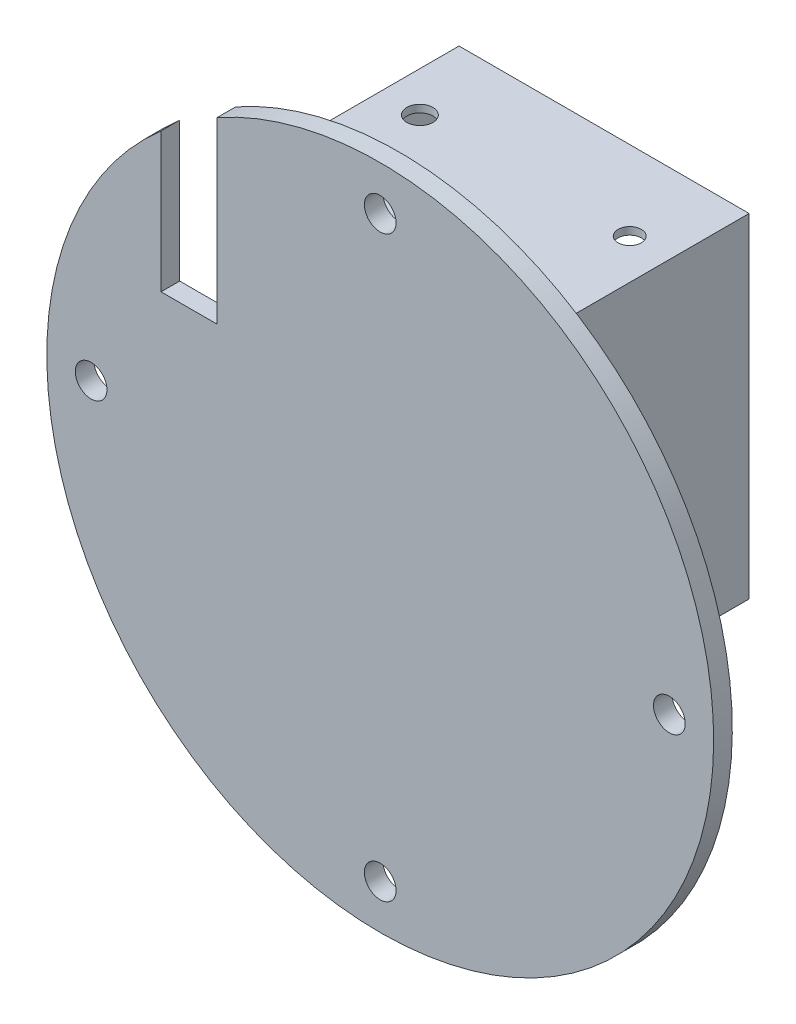
SolidWorks part; units mm, degrees
ref_plane "Front Plane" through (0, 0, 0) normal (0, 0, 1) x (1, 0, 0)
ref_plane "Top Plane" through (0, 0, 0) normal (0, 1, 0) x (1, 0, 0)
ref_plane "Right Plane" through (0, 0, 0) normal (1, 0, 0) x (0, 0, -1)
sketch "Sketch1" plane through (0, 0, 0) normal (0, 0, 1) x (1, 0, 0)
  circle A0 centre (0, 0) radius 35.75
  dimension "D1" = 71.5
extrude "Boss-Extrude1" add sketch "Sketch1" along normal blind 2 contours A0
sketch "Sketch2" plane through (0, 0, 0) normal (0, 0, -1) x (-1, 0, 0)
  line L52 (14.75, 26) -> (-14.75, 26)
  line L59 (15.55, -9) -> (15.55, 26.8)
  line L60 (15.55, 26.8) -> (-15.55, 26.8)
  line L61 (-15.55, 26.8) -> (-15.55, -9)
  line L68 (-14.75, 26) -> (-14.75, -9)
  line L70 (14.75, 26) -> (14.75, -9)
  line L71 (14.75, -9) -> (15.55, -9)
  line L72 (-14.75, -9) -> (-15.55, -9)
  dimension "D1" = 35
  dimension "D2" = 29.5
  dimension "D3" = 0.8
  dimension "D4" = 0.8
  dimension "D5" = 35
  dimension "D6" = 0.8
  dimension "D7" = 26
  dimension "D8" = 14.75
extrude "Boss-Extrude2" add sketch "Sketch2" along normal blind 22
sketch "Sketch3" plane through (0, 0, 0) normal (0, 0, -1) x (-1, 0, 0)
  line L1 (-14.75, 26) -> (14.75, 26)
  line L2 (-14.75, 26) -> (-14.75, -9)
  line L3 (-14.75, -9) -> (14.75, -9)
  line L4 (14.75, 26) -> (14.75, -9)
extrude "Boss-Extrude3" add sketch "Sketch3" along normal blind 10
sketch "Sketch4" plane through (0, 26, 0) normal (0, -1, 0) x (1, 0, 0)
  line L1 (14.75, -10) -> (-14.75, -10) construction
  line L2 (-14.75, -22) -> (-14.75, -10) construction
  line L3 (-14.75, -10) -> (14.75, -10) construction
  line L4 (14.75, -22) -> (14.75, -10) construction
  circle A0 centre (-11.25, -13.5) radius 1.4
  circle A1 centre (11.25, -13.5) radius 1.25
  dimension "D1" = 2.8
  dimension "D2" = 2.5
  dimension "D3" = 3.5
  dimension "D4" = 3.5
  dimension "D5" = 3.5
  dimension "D6" = 3.5
extrude "Cut-Extrude1" cut sketch "Sketch4" against normal blind 2
sketch "Sketch5" plane through (0, 0, 2) normal (0, 0, 1) x (1, 0, 0)
  line L0 (0, 0) -> (-35.75, 0)
  line L1 (-17.5, 0) -> (-17.5, 12)
  line L7 (-17.5, 12) -> (-23.5, 12)
  line L8 (-23.5, 12) -> (-23.5, 22.1318)
  line L9 (-23.5, 22.1318) -> (-17.5, 22)
  line L10 (-17.5, 22) -> (-17.5, 12)
  circle A0 centre (0, 0) radius 35.75 construction
  dimension "D1" = 17.5
  dimension "D2" = 12
  dimension "D3" = 10
  dimension "D4" = 6
extrude "Cut-Extrude2" cut sketch "Sketch5" against normal blind 10 contours L7 L8 L9 L10
sketch "Sketch6" plane through (0, 0, 2) normal (0, 0, 1) x (1, 0, 0)
  line L0 (0, 0) -> (-31, 0)
  line L1 (0, 0) -> (0, 31)
  circle A0 centre (0, 31) radius 1.7
  circle A1 centre (-31, 0) radius 1.7
  circle A2 centre (31, 0) radius 1.7
  circle A3 centre (0, -31) radius 1.7
  dimension "D1" = 3.4
  dimension "D2" = 3.4
  dimension "D3" = 31
  dimension "D4" = 31
extrude "Cut-Extrude3" cut sketch "Sketch6" against normal blind 34 contours A0 | A1 | A2 | A3 region at (-32.6519, 0, 2) region at (-1.1681, 32.1681, 2) region at (31, 0, 2)
sketch "Sketch7" plane through (0, 0, 2) normal (0, 0, 1) x (1, 0, 0)
  line L0 (-17.5, 12) -> (-23.5, 12) construction
  line L1 (-17.5, 22) -> (-17.5, 12) construction
  line L2 (-23.5, 12) -> (-23.5, 22.1318) construction
  line L4 (-17.5, 12) -> (-23.5, 12)
  line L5 (-17.5, 35.7947) -> (-17.5, 12)
  line L6 (-23.5, 12) -> (-23.5, 35.9265)
  line L7 (-23.5, 35.9265) -> (-17.5, 35.7947)
extrude "Cut-Extrude4" cut sketch "Sketch7" against normal blind 10
